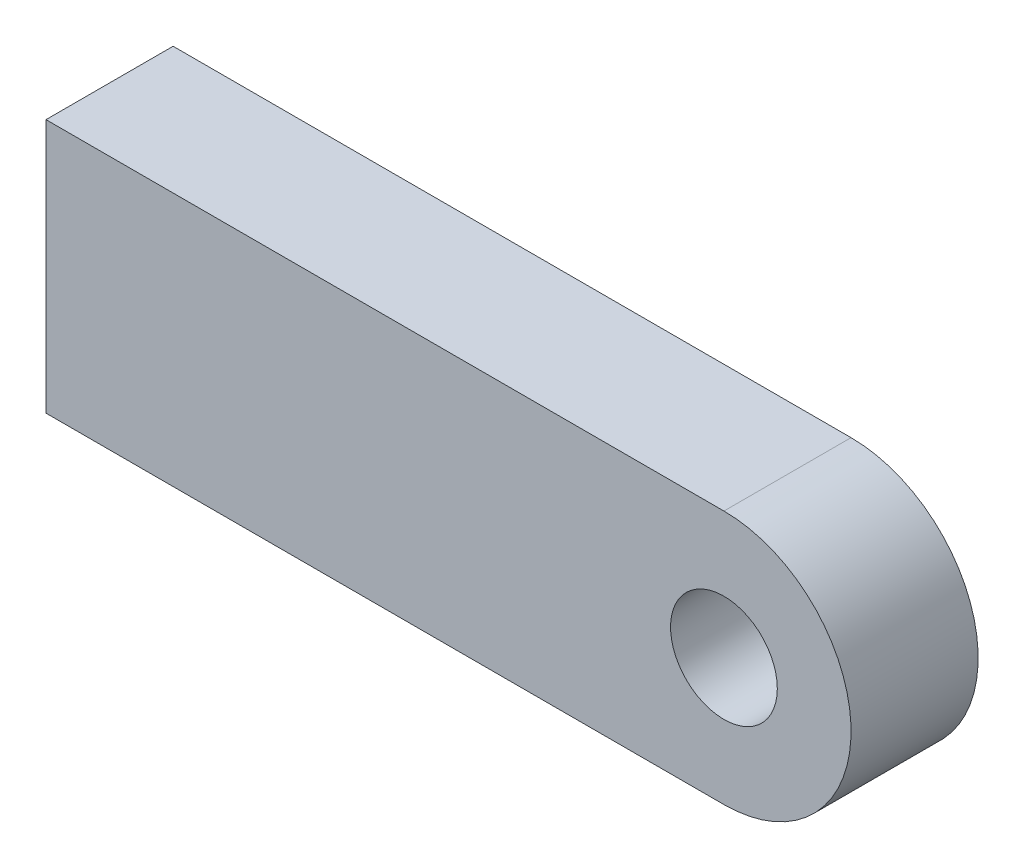
SolidWorks part; units mm, degrees
ref_plane "Front Plane" through (0, 0, 0) normal (0, 0, 1) x (1, 0, 0)
ref_plane "Top Plane" through (0, 0, 0) normal (0, 1, 0) x (1, 0, 0)
ref_plane "Right Plane" through (0, 0, 0) normal (1, 0, 0) x (0, 0, -1)
sketch "Sketch1" plane through (0, 0, 1568.0737) normal (0, 0, 1) x (1, 0, 0)
  line L0 (226.7802, 617.2016) -> (175.9802, 617.2016) construction
  line L1 (226.7802, 617.2016) -> (175.9802, 617.2016)
  line L2 (197.4735, 617.2016) -> (197.4735, 626.7266) construction
  line L3 (175.9802, 626.7266) -> (236.3531, 626.7266)
  line L4 (175.9802, 626.7266) -> (175.9802, 607.6766)
  line L5 (175.9802, 607.6766) -> (236.3531, 607.6766)
  line L6 (236.3531, 626.7266) -> (236.3531, 607.6766)
  line L7 (207.2393, 617.2016) -> (207.2393, 607.6766) construction
  line L8 (236.3531, 617.2016) -> (226.7802, 617.2016) construction
  circle A2 centre (226.7802, 617.2016) radius 4 construction
  circle A3 centre (226.7802, 617.2016) radius 4
  arc A4 (226.7802, 626.7266) -> (226.7802, 607.6766) centre (226.7802, 617.2016) cw
  point P13 (175.9802, 617.2016)
  point P17 (0, 0)
  point P18 (0, 0)
  point P19 (0, 0)
  point P20 (0, 0)
extrude "Boss-Extrude1" add sketch "Sketch1" along normal blind 4.7625 and the other way blind 4.7625 contours L4 L5 L3 region at (176.6129, 621.9641, 1568.0737)
sketch "Sketch2" plane through (175.9802, 0, 0) normal (-1, 0, 0) x (0, 0, 1)
  line L1 (1571.425, 630.6431) -> (1564.7223, 603.7601) construction
  line L5 (1588.5254, 626.3795) -> (1556.524, 634.3583) construction
  line L11 (1549.5134, 607.5521) -> (1581.126, 599.6702) construction
  line L13 (1568.0737, 617.2016) -> (1571.425, 630.6431) construction
  line L14 (1563.3112, 607.6766) -> (1572.8362, 607.6766) construction
  line L15 (1572.8362, 626.7266) -> (1572.8362, 607.6766) construction
  line L16 (1563.3112, 626.7266) -> (1572.8362, 626.7266)
  line L17 (1563.3112, 626.7266) -> (1563.3112, 607.6766)
  line L18 (1563.3112, 607.6766) -> (1572.8362, 607.6766)
  line L19 (1572.8362, 626.7266) -> (1572.8362, 607.6766)
  line L22 (1540.6497, 609.7621) -> (1547.3523, 636.6451)
  line L23 (1540.6497, 609.7621) -> (1588.795, 597.7581)
  line L24 (1547.3523, 636.6451) -> (1595.4977, 624.6411)
  line L25 (1588.795, 597.7581) -> (1595.4977, 624.6411)
  point P5 (1568.0737, 617.2016)
  point P21 (1568.0737, 617.2016)
  point P23 (1568.0737, 617.2016)
sketch "Sketch5" plane through (0, 0, 1572.8362) normal (0, 0, 1) x (1, 0, 0)
  line L0 (179.0527, 629.5244) -> (172.9078, 604.8788)
  line L1 (179.0527, 629.5244) -> (163.5133, 629.5244)
  point P0 (164.7542, 631.8127)
  point P2 (175.9802, 617.2016)
